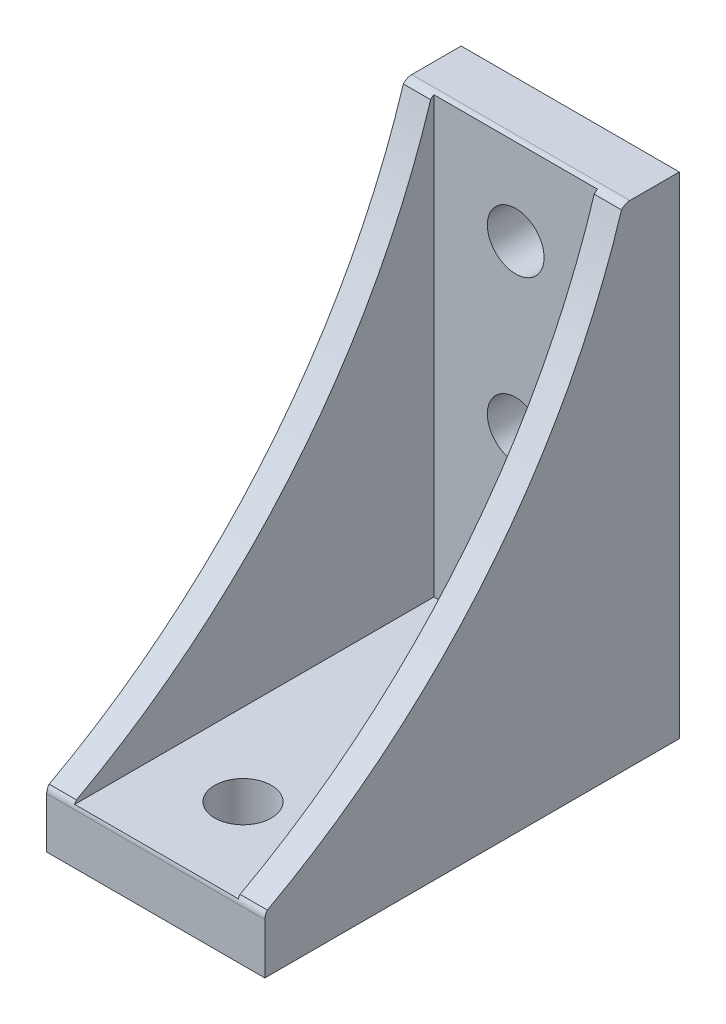
SolidWorks part; units mm, degrees
ref_plane "前基準面" through (0, 0, 0) normal (0, 0, 1) x (1, 0, 0)
ref_plane "上基準面" through (0, 0, 0) normal (0, 1, 0) x (1, 0, 0)
ref_plane "右基準面" through (0, 0, 0) normal (1, 0, 0) x (0, 0, -1)
ref_plane "平面1" through (0, 0, 0) normal (1, 0, 0) x (0, 0, -1)
sketch "草圖1" plane through (0, 0, 0) normal (1, 0, 0) x (0, 0, -1)
  line L0 (-38, 0) -> (0, 0)
  line L1 (0, 0) -> (0, 45)
  line L2 (0, 45) -> (-4.5286, 45)
  line L3 (-5.3, 44.6364) -> (-37.7714, 5.2771)
  line L4 (-38, 4.6407) -> (-38, 0)
  arc A0 (-4.5286, 45) -> (-5.3, 44.6364) centre (-4.5286, 44) ccw
  arc A1 (-37.7714, 5.2771) -> (-38, 4.6407) centre (-37, 4.6407) ccw
extrude "填料-伸長1" add sketch "草圖1" against normal blind 10 and the other way blind 10
ref_plane "平面2" through (0, 0, 0) normal (1, 0, 0) x (0, 0, -1)
sketch "草圖2" plane through (0, 0, 0) normal (1, 0, 0) x (0, 0, -1)
  line L0 (-43, 5) -> (-5, 5)
  line L1 (-5, 5) -> (-5, 50)
  line L2 (-5, 50) -> (-43, 50)
  line L3 (-43, 50) -> (-43, 5)
extrude "除料-伸長1" cut sketch "草圖2" against normal blind 7.5 and the other way blind 7.5
ref_plane "平面3" through (0, 0, 0) normal (1, 0, 0) x (0, 0, -1)
sketch "草圖3" plane through (0, 0, 0) normal (1, 0, 0) x (0, 0, -1)
  line L0 (-5.3, 44.6364) -> (-37.7714, 5.2771)
  arc A0 (-37.7714, 5.2771) -> (-5.3, 44.6364) centre (-69.8148, 64.787) ccw
extrude "除料-伸長2" cut sketch "草圖3" against normal blind 10 and the other way blind 10
ref_plane "平面4" through (0, 0, 0) normal (0, 1, 0) x (1, 0, 0)
sketch "草圖4" plane through (0, 0, 0) normal (0, 1, 0) x (1, 0, 0)
  circle A0 centre (0, -10) radius 2.6
extrude "除料-伸長3" cut sketch "草圖4" along normal blind 5
ref_plane "平面5" through (0, 0, 0) normal (0, 1, 0) x (1, 0, 0)
sketch "草圖5" plane through (0, 0, 0) normal (0, 1, 0) x (1, 0, 0)
  circle A0 centre (0, -30) radius 2.6
extrude "除料-伸長4" cut sketch "草圖5" along normal blind 5
ref_plane "平面6" through (0, 0, 0) normal (0, 0, 1) x (1, 0, 0)
sketch "草圖6" plane through (0, 0, 0) normal (0, 0, 1) x (1, 0, 0)
  circle A0 centre (0, 22) radius 2.6
extrude "除料-伸長5" cut sketch "草圖6" along normal blind 5
ref_plane "平面7" through (0, 0, 0) normal (0, 0, 1) x (1, 0, 0)
sketch "草圖7" plane through (0, 0, 0) normal (0, 0, 1) x (1, 0, 0)
  circle A0 centre (0, 37) radius 2.6
extrude "除料-伸長6" cut sketch "草圖7" along normal blind 5
ref_plane "平面8" through (0, 0, 0) normal (0, 1, 0) x (1, 0, 0)
sketch "草圖8" plane through (0, 0, 0) normal (0, 1, 0) x (1, 0, 0)
  line L0 (-10, 0) -> (-10, -38)
  line L1 (-10, -38) -> (10, -38)
  line L2 (10, -38) -> (10, 0)
  line L3 (10, 0) -> (-10, 0)
extrude "填料-伸長2" add sketch "草圖8" against normal blind 0.8
ref_plane "平面9" through (0, 0, 0) normal (0, 0, 1) x (1, 0, 0)
sketch "草圖9" plane through (0, 0, 0) normal (0, 0, 1) x (1, 0, 0)
  line L0 (-10, 0) -> (10, 0)
  line L1 (10, 0) -> (10, 45)
  line L2 (10, 45) -> (-10, 45)
  line L3 (-10, 45) -> (-10, 0)
extrude "填料-伸長3" add sketch "草圖9" against normal blind 0.8
ref_plane "平面10" through (0, 0, 0) normal (0, 1, 0) x (1, 0, 0)
sketch "草圖10" plane through (0, 0, 0) normal (0, 1, 0) x (1, 0, 0)
  line L0 (-10, 0) -> (-10, -38)
  line L1 (-10, -38) -> (10, -38)
  line L2 (10, -38) -> (10, 0)
  line L3 (10, 0) -> (-10, 0)
  line L4 (0.5, -33) -> (2, -33)
  line L5 (3, -32) -> (3, -30.5)
  line L6 (3, -30.5) -> (2.5515, -30.5)
  line L7 (0.5, -32.5515) -> (0.5, -33)
  line L8 (0.5, -27) -> (0.5, -27.4485)
  line L9 (2.5515, -29.5) -> (3, -29.5)
  line L10 (3, -29.5) -> (3, -28)
  line L11 (2, -27) -> (0.5, -27)
  line L12 (0.5, -13) -> (2, -13)
  line L13 (3, -12) -> (3, -10.5)
  line L14 (3, -10.5) -> (2.5515, -10.5)
  line L15 (0.5, -12.5515) -> (0.5, -13)
  line L16 (0.5, -7) -> (0.5, -7.4485)
  line L17 (2.5515, -9.5) -> (3, -9.5)
  line L18 (3, -9.5) -> (3, -8)
  line L19 (2, -7) -> (0.5, -7)
  line L20 (-2, -33) -> (-0.5, -33)
  line L21 (-0.5, -33) -> (-0.5, -32.5515)
  line L22 (-2.5515, -30.5) -> (-3, -30.5)
  line L23 (-3, -30.5) -> (-3, -32)
  line L24 (-3, -29.5) -> (-2.5515, -29.5)
  line L25 (-0.5, -27.4485) -> (-0.5, -27)
  line L26 (-0.5, -27) -> (-2, -27)
  line L27 (-3, -28) -> (-3, -29.5)
  line L28 (-2, -13) -> (-0.5, -13)
  line L29 (-0.5, -13) -> (-0.5, -12.5515)
  line L30 (-2.5515, -10.5) -> (-3, -10.5)
  line L31 (-3, -10.5) -> (-3, -12)
  line L32 (-3, -9.5) -> (-2.5515, -9.5)
  line L33 (-0.5, -7.4485) -> (-0.5, -7)
  line L34 (-0.5, -7) -> (-2, -7)
  line L35 (-3, -8) -> (-3, -9.5)
  arc A0 (2, -33) -> (3, -32) centre (2, -32) ccw
  arc A1 (2.5515, -30.5) -> (0.5, -32.5515) centre (0, -30) cw
  arc A2 (0.5, -27.4485) -> (2.5515, -29.5) centre (0, -30) cw
  arc A3 (3, -28) -> (2, -27) centre (2, -28) ccw
  arc A4 (2, -13) -> (3, -12) centre (2, -12) ccw
  arc A5 (2.5515, -10.5) -> (0.5, -12.5515) centre (0, -10) cw
  arc A6 (0.5, -7.4485) -> (2.5515, -9.5) centre (0, -10) cw
  arc A7 (3, -8) -> (2, -7) centre (2, -8) ccw
  arc A8 (-3, -32) -> (-2, -33) centre (-2, -32) ccw
  arc A9 (-0.5, -32.5515) -> (-2.5515, -30.5) centre (0, -30) cw
  arc A10 (-2.5515, -29.5) -> (-0.5, -27.4485) centre (0, -30) cw
  arc A11 (-2, -27) -> (-3, -28) centre (-2, -28) ccw
  arc A12 (-3, -12) -> (-2, -13) centre (-2, -12) ccw
  arc A13 (-0.5, -12.5515) -> (-2.5515, -10.5) centre (0, -10) cw
  arc A14 (-2.5515, -9.5) -> (-0.5, -7.4485) centre (0, -10) cw
  arc A15 (-2, -7) -> (-3, -8) centre (-2, -8) ccw
extrude "除料-伸長7" cut sketch "草圖10" against normal blind 0.8
ref_plane "平面11" through (0, 0, 0) normal (0, 0, 1) x (1, 0, 0)
sketch "草圖11" plane through (0, 0, 0) normal (0, 0, 1) x (1, 0, 0)
  line L0 (-10, 45) -> (-10, 0)
  line L1 (-10, 0) -> (10, 0)
  line L2 (10, 0) -> (10, 45)
  line L3 (10, 45) -> (-10, 45)
  line L4 (-2.7, 27) -> (2.7, 27)
  line L5 (3, 27.3) -> (3, 32.7)
  line L6 (2.7, 33) -> (-2.7, 33)
  line L7 (-3, 32.7) -> (-3, 27.3)
  line L8 (-2.7, 3) -> (2.7, 3)
  line L9 (3, 3.3) -> (3, 7.7)
  line L10 (2.7, 8) -> (-2.7, 8)
  line L11 (-3, 7.7) -> (-3, 3.3)
  arc A0 (-3, 27.3) -> (-2.7, 27) centre (-2.7, 27.3) ccw
  arc A1 (2.7, 27) -> (3, 27.3) centre (2.7, 27.3) ccw
  arc A2 (3, 32.7) -> (2.7, 33) centre (2.7, 32.7) ccw
  arc A3 (-2.7, 33) -> (-3, 32.7) centre (-2.7, 32.7) ccw
  arc A4 (-3, 3.3) -> (-2.7, 3) centre (-2.7, 3.3) ccw
  arc A5 (2.7, 3) -> (3, 3.3) centre (2.7, 3.3) ccw
  arc A6 (3, 7.7) -> (2.7, 8) centre (2.7, 7.7) ccw
  arc A7 (-2.7, 8) -> (-3, 7.7) centre (-2.7, 7.7) ccw
extrude "除料-伸長8" cut sketch "草圖11" against normal blind 1.25
